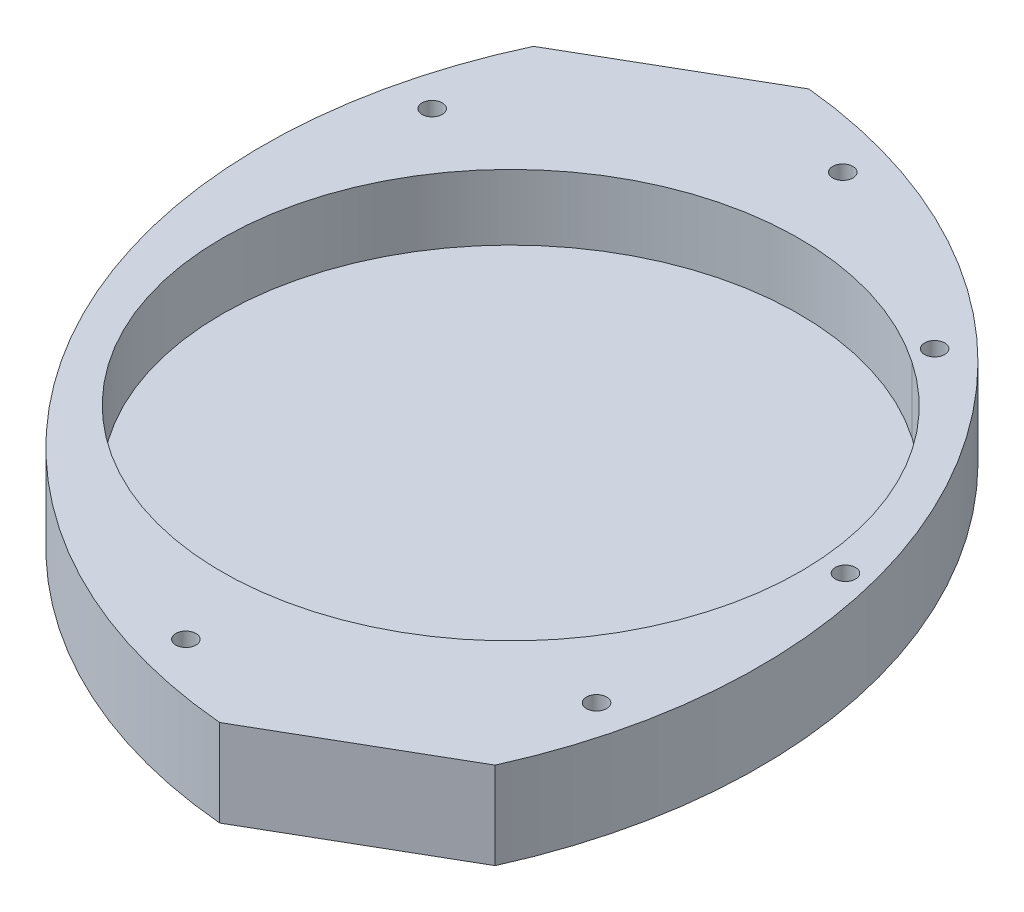
SolidWorks part; units mm, degrees
ref_plane "Front Plane" through (0, 0, 0) normal (0, 0, 1) x (1, 0, 0)
ref_plane "Top Plane" through (0, 0, 0) normal (0, 1, 0) x (1, 0, 0)
ref_plane "Right Plane" through (0, 0, 0) normal (1, 0, 0) x (0, 0, -1)
sketch "Sketch1" plane through (0, 0, 0) normal (0, 1, 0) x (1, 0, 0)
  line L4 (22.6902, -19.0005) -> (5.1098, -29.1505) construction
  line L5 (-22.6902, 19.0005) -> (-5.1098, 29.1505) construction
  line L6 (22.6902, -19.0005) -> (5.1098, -29.1505) construction
  line L7 (-22.6902, 19.0005) -> (-5.1098, 29.1505) construction
  line L8 (-3.6098, 26.5524) -> (-21.1902, 16.4024)
  line L9 (21.1902, -16.4024) -> (-3.6098, 26.5524)
  line L10 (3.6098, -26.5524) -> (21.1902, -16.4024)
  line L11 (-21.1902, 16.4024) -> (3.6098, -26.5524)
  line L12 (-3.6098, 26.5524) -> (-21.1902, 16.4024) construction
  line L13 (21.1902, -16.4024) -> (-3.6098, 26.5524) construction
  line L14 (3.6098, -26.5524) -> (21.1902, -16.4024) construction
  line L15 (-21.1902, 16.4024) -> (3.6098, -26.5524) construction
  line L20 (-26.6855, 19.7383) -> (-3.4358, 33.1615)
  line L21 (-26.6855, 19.7383) -> (3.6098, -32.7347)
  line L22 (-3.4358, 33.1615) -> (26.8595, -19.3115)
  line L23 (3.6098, -32.7347) -> (26.8595, -19.3115)
  dimension "D1" = 0
extrude "Boss-Extrude1" add sketch "Sketch1" along normal mid plane 16.51
sketch "Sketch2" plane through (0, 8.255, 0) normal (0, 1, 0) x (1, 0, 0)
  circle A0 centre (0, 0) radius 4.5217
extrude "Cut-Extrude1" cut sketch "Sketch2" against normal blind 24.892
sketch "Sketch3" plane through (0, 8.255, 0) normal (0, 1, 0) x (1, 0, 0)
  line L0 (-10.3143, 73.7392) -> (-58.7029, 45.802)
  line L1 (-10.3143, 73.7392) -> (58.7029, -45.802)
  line L2 (-58.7029, 45.802) -> (10.3143, -73.7392)
  line L3 (58.7029, -45.802) -> (10.3143, -73.7392)
  line L4 (-26.6855, 19.7383) -> (3.6098, -32.7347)
  line L6 (-26.6855, 19.7383) -> (3.6098, -32.7347)
  line L12 (3.6098, -32.7347) -> (26.8595, -19.3115)
  line L14 (3.6098, -32.7347) -> (26.8595, -19.3115)
  line L16 (26.8595, -19.3115) -> (-3.4358, 33.1615)
  line L17 (26.8595, -19.3115) -> (-3.4358, 33.1615)
  line L18 (-3.4358, 33.1615) -> (-26.6855, 19.7383)
  line L19 (-3.4358, 33.1615) -> (-26.6855, 19.7383)
  line L20 (-10.3143, 73.7392) -> (10.3143, -73.7392) construction
  line L21 (58.7029, -45.802) -> (-58.7029, 45.802) construction
  line M30 (-26.6855, 19.7383) -> (3.6098, -32.7347)
  line M31 (3.6098, -32.7347) -> (26.8595, -19.3115)
  line M32 (26.8595, -19.3115) -> (-3.4358, 33.1615)
  line M33 (-3.4358, 33.1615) -> (-26.6855, 19.7383)
  dimension "D2" = 0
extrude "Boss-Extrude2" add sketch "Sketch3" along normal blind 2.54 and the other way blind 19.05 separate body contours L3 L1 L0 L2 M30 M33 M32 M31 region at (22.5618, 8.255, -13.0261)
sketch "Sketch7" plane through (-24.1943, 0, 13.9686) normal (-0.866, 0, 0.5) x (0.5, 0, 0.866)
  line L12 (-90.6072, 10.795) -> (-118.9293, -90.805)
  line L13 (-69.0172, 10.795) -> (-90.6072, 10.795)
  line L14 (-69.0172, 10.795) -> (-69.0172, -10.795)
  line L17 (-118.9293, -90.805) -> (-97.3393, -90.805)
  line L18 (-97.3393, -90.805) -> (-69.0172, -10.795)
  line L19 (-69.0172, 10.795) -> (69.0172, 10.795) construction
  dimension "D2" = 101.6
  dimension "D3" = 21.59
  dimension "D4" = 21.59
extrude "Boss-Extrude3" add sketch "Sketch7" against normal up to surface (55.8744 mm away) up to face at (24.1943, 0, -13.9686)
sketch "Sketch8" plane through (-24.1943, 0, 13.9686) normal (-0.866, 0, 0.5) x (0.5, 0, 0.866)
  line L0 (-118.9293, -90.805) -> (-97.3393, -90.805) construction
  line L1 (-153.2465, -90.805) -> (153.2465, -90.805)
  line L2 (-153.2465, -90.805) -> (-153.2465, -109.855)
  line L3 (-153.2465, -109.855) -> (153.2465, -109.855)
  line L4 (153.2465, -90.805) -> (153.2465, -109.855)
  point P10 (0, -90.805)
  dimension "D1" = 19.05
extrude "Boss-Extrude4" add sketch "Sketch8" against normal up to surface (55.8744 mm away) up to face at (4.3728, -30.2683, -48.3005)
ref_plane "Plane1" through (-0.0707, 0, -0.1224) normal (0.5, 0, 0.866) x (0.866, 0, -0.5)
mirror "Mirror1" about plane through (-0.0707, 0, -0.1224) normal (0.5, 0, 0.866) of "Boss-Extrude3"
sketch "Sketch9" plane through (0, -90.805, 0) normal (0, 1, 0) x (1, 0, 0)
  circle A0 centre (0, 0) radius 88.9
  dimension "D1" = 177.8
extrude "Boss-Extrude5" add sketch "Sketch9" against normal blind 19.05
sketch "Sketch10" plane through (-24.1943, 0, 13.9686) normal (-0.866, 0, 0.5) x (0.5, 0, 0.866)
  line L1 (-98, -75.1628) -> (93.7668, -75.1628)
  line L2 (-98, -75.1628) -> (-98, -61.6348)
  line L3 (-98, -61.6348) -> (93.7668, -61.6348)
  line L4 (93.7668, -75.1628) -> (93.7668, -61.6348)
extrude "Boss-Extrude6" add sketch "Sketch10" against normal up to surface (55.8744 mm away) up to face at (24.159, -72.8663, -14.0298)
sketch "Sketch12" plane through (0, 8.255, 0) normal (0, 1, 0) x (1, 0, 0)
  circle A1 centre (0, 0) radius 3.05
  circle A2 centre (0, 0) radius 3.05
  circle A3 centre (-11.8785, 10.5333) radius 1.75
  circle A4 centre (-11.8785, 10.5333) radius 1.75
  circle A5 centre (-1.8376, -6.8581) radius 1.75
  circle A6 centre (-1.8376, -6.8581) radius 1.75
  circle A7 centre (11.8785, -10.5333) radius 1.75
  circle A8 centre (11.8785, -10.5333) radius 1.75
  circle A9 centre (1.8376, 6.8581) radius 1.75
  circle A10 centre (1.8376, 6.8581) radius 1.75
  circle A11 centre (-3.1828, 15.5538) radius 1.75
  circle A12 centre (-3.1828, 15.5538) radius 1.75
  circle A13 centre (3.1828, -15.5538) radius 1.75
  circle A14 centre (3.1828, -15.5538) radius 1.75
  circle A15 centre (-6.8581, 1.8376) radius 1.75
  circle A16 centre (-6.8581, 1.8376) radius 1.75
  circle A17 centre (6.8581, -1.8376) radius 1.75
  circle A18 centre (6.8581, -1.8376) radius 1.75
  dimension "D1" = 0
  dimension "D2" = 0
  dimension "D3" = 0
  dimension "D4" = 0
  dimension "D5" = 0
  dimension "D6" = 0
  dimension "D7" = 0
  dimension "D8" = 0
  dimension "D9" = 0
extrude "Cut-Extrude3" cut sketch "Sketch12" against normal blind 25.146 contours A12 | A14 | A4 | A8 region at (-3.1828, 8.255, -15.5538) region at (3.1828, 8.255, 15.5538)
sketch "Sketch14" plane through (0, 10.795, 0) normal (0, 1, 0) x (1, 0, 0)
  circle A0 centre (24.1201, -48.1662) radius 12.7008
extrude "Cut-Extrude4" cut sketch "Sketch14" against normal blind 30.48
mirror "Mirror2" about plane through (-0.0707, 0, -0.1224) normal (0.5, 0, 0.866) of "Cut-Extrude4"
sketch "Sketch15" plane through (0, -90.805, 0) normal (0, 1, 0) x (1, 0, 0)
  line L0 (100.8176, -118.7468) -> (83.5177, -88.7825) construction
  line L1 (83.5177, -88.7825) -> (35.129, -116.7197) construction
  line L2 (35.129, -116.7197) -> (52.4289, -146.684) construction
  line L3 (52.4289, -146.684) -> (100.8176, -118.7468) construction
  line L4 (-83.659, 89.0272) -> (-35.2703, 116.9644) construction
  line L5 (-35.2703, 116.9644) -> (-52.4289, 146.684) construction
  line L6 (-52.4289, 146.684) -> (-100.8176, 118.7468) construction
  line L7 (-100.8176, 118.7468) -> (-83.659, 89.0272) construction
  line L8 (100.8176, -118.7468) -> (83.5177, -88.7825)
  line L9 (83.5177, -88.7825) -> (35.129, -116.7197)
  line L10 (35.129, -116.7197) -> (52.4289, -146.684)
  line L11 (52.4289, -146.684) -> (100.8176, -118.7468)
  line L12 (-83.659, 89.0272) -> (-35.2703, 116.9644)
  line L13 (-35.2703, 116.9644) -> (-52.4289, 146.684)
  line L14 (-52.4289, 146.684) -> (-100.8176, 118.7468)
  line L15 (-100.8176, 118.7468) -> (-83.659, 89.0272)
extrude "Cut-Extrude5" cut sketch "Sketch15" against normal blind 55.118
sketch "Sketch16" plane through (0, -90.805, 0) normal (0, 1, 0) x (1, 0, 0)
  circle A0 centre (0, 0) radius 79.375
  dimension "D1" = 158.75
extrude "Cut-Extrude6" cut sketch "Sketch16" against normal blind 16.129
sketch "Sketch17" plane through (0, 10.795, 0) normal (0, 1, 0) x (1, 0, 0)
  line L8 (27.8239, -104.0669) -> (76.2126, -76.1297)
  line L9 (76.2126, -76.1297) -> (-31.0179, 109.5989)
  line L10 (-31.0179, 109.5989) -> (-79.4065, 81.6617)
  line L11 (-79.4065, 81.6617) -> (27.8239, -104.0669)
extrude "Cut-Extrude7" cut sketch "Sketch17" against normal blind 8.89
sketch "Sketch18" plane through (0, 1.905, 0) normal (0, 1, 0) x (1, 0, 0)
  line L4 (-26.6855, 19.7383) -> (3.6098, -32.7347)
  line L5 (3.6098, -32.7347) -> (26.8595, -19.3115)
  line L6 (26.8595, -19.3115) -> (-3.4358, 33.1615)
  line L7 (-3.4358, 33.1615) -> (-26.6855, 19.7383)
  line L8 (-26.6855, 19.7383) -> (3.6098, -32.7347)
  line L9 (3.6098, -32.7347) -> (26.8595, -19.3115)
  line L10 (26.8595, -19.3115) -> (-3.4358, 33.1615)
  line L11 (-3.4358, 33.1615) -> (-26.6855, 19.7383)
  dimension "D1" = 0
extrude "Cut-Extrude8" cut sketch "Sketch18" against normal blind 2.54
sketch "Sketch19" plane through (-24.1943, 0, 13.9686) normal (-0.866, 0, 0.5) x (0.5, 0, 0.866)
  line L0 (-69.0172, -10.795) -> (68.7346, -10.795) construction
  line L1 (-141.7946, -10.795) -> (140.3794, -10.795)
  line L2 (-141.7946, -10.795) -> (-141.7946, -90.805)
  line L3 (-141.7946, -90.805) -> (140.3794, -90.805)
  line L4 (140.3794, -10.795) -> (140.3794, -90.805)
extrude "Cut-Extrude9" cut sketch "Sketch19" against normal blind 75.946
move or copy body "Body-Move/Copy1" bodies to move or copy 134 132 copy no translate (0, -38.1, 0) parameters "D1"=0, "D2"=0, "D3"=0
combine bodies "Combine1" operation type add bodies to combine 135 136
delete or keep bodies "Body-Delete/Keep 1" type delete bodies bodies 137
sketch "Sketch20" plane through (0, -109.855, 0) normal (0, -1, 0) x (1, 0, 0)
  line L2 (-83.659, -89.0272) -> (-35.2703, -116.9644)
  line L3 (83.5177, 88.7825) -> (35.129, 116.7197)
  line L4 (-83.659, -89.0272) -> (-35.2703, -116.9644)
  line L5 (83.5177, 88.7825) -> (35.129, 116.7197)
  circle A1 centre (0, 0) radius 79.375
  circle A6 centre (0, 0) radius 79.375
  arc A8 (-35.2703, -116.9644) -> (83.5177, 88.7825) centre (-49.7044, 28.5337) ccw
  arc A9 (-35.2703, -116.9644) -> (83.5177, 88.7825) centre (-49.7044, 28.5337) ccw
  arc A10 (35.129, 116.7197) -> (-83.659, -89.0272) centre (47.4504, -27.5587) ccw
  arc A11 (35.129, 116.7197) -> (-83.659, -89.0272) centre (47.4504, -27.5587) ccw
  dimension "D1" = 0
  dimension "D2" = 0
extrude "Boss-Extrude7" add sketch "Sketch20" against normal up to surface (19.05 mm away) up to face at (0, -90.805, 79.375)
sketch "Sketch21" plane through (0, -90.805, 0) normal (0, 1, 0) x (1, 0, 0)
  line L0 (-13.2715, 22.9869) -> (13.2715, -22.9869) construction
  line L1 (-47.7021, -27.3776) -> (47.5607, 27.6224) construction
  circle A1 centre (-10.6119, 101.6801) radius 2.8
  circle A2 centre (-82.7516, 60.0302) radius 2.8
  circle A3 centre (82.6103, -59.7854) radius 2.8
  circle A4 centre (10.4705, -101.4353) radius 2.8
  circle A5 centre (44.4771, 72.0355) radius 2.794
  circle A6 centre (86.011, 5.7939) radius 2.794
  point P0 (82.6103, -59.7854)
  point P7 (10.4705, -101.4353)
  point P12 (-82.7516, 60.0302)
  point P13 (-10.6119, 101.6801)
  dimension "D1" = 5.6
  dimension "D2" = 5.588
  dimension "D3" = 5.588
extrude "Cut-Extrude10" cut sketch "Sketch21" against normal blind 9.1
ref_axis "Axis1" through (0, -14.0367, 0) along (0, 1, 0)
sketch "Sketch22" plane through (0, -90.805, 0) normal (0, 1, 0) x (1, 0, 0)
  circle A0 centre (0, 0) radius 79.375
extrude "Cut-Extrude11" cut sketch "Sketch22" against normal blind 18.161
sketch "Sketch23" plane through (0, -109.855, 0) normal (0, -1, 0) x (1, 0, 0)
  line L2 (-83.659, -89.0272) -> (-35.2703, -116.9644)
  line L6 (-83.659, -89.0272) -> (-35.2703, -116.9644)
  line L7 (83.5177, 88.7825) -> (35.129, 116.7197)
  line L8 (83.5177, 88.7825) -> (35.129, 116.7197)
  arc A2 (-35.2703, -116.9644) -> (83.5177, 88.7825) centre (-49.7044, 28.5337) ccw
  arc A11 (-35.2703, -116.9644) -> (83.5177, 88.7825) centre (-49.7044, 28.5337) ccw
  arc A12 (35.129, 116.7197) -> (-83.659, -89.0272) centre (47.4504, -27.5587) ccw
  arc A13 (35.129, 116.7197) -> (-83.659, -89.0272) centre (47.4504, -27.5587) ccw
  dimension "D1" = 0
extrude "Boss-Extrude8" add sketch "Sketch23" along normal blind 5.08
sketch "Sketch24" plane through (0, -90.805, 0) normal (0, 1, 0) x (1, 0, 0)
  line L0 (-47.7021, -27.3776) -> (47.5607, 27.6224) construction
  circle A0 centre (-0.7398, -0.2639) radius 80.01
  dimension "D1" = 160.02
extrude "Cut-Extrude12" cut sketch "Sketch24" against normal up to surface (18.161 mm away) up to face at (0, -108.966, 79.375)
